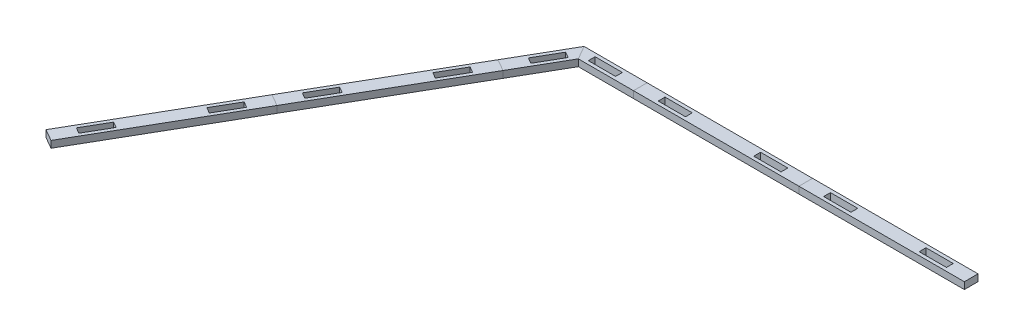
SolidWorks part; units mm, degrees
material "Cedar"
ref_plane "Front Plane" through (0, 0, 0) normal (0, 0, 1) x (1, 0, 0)
ref_plane "Top Plane" through (0, 0, 0) normal (0, 1, 0) x (1, 0, 0)
ref_plane "Right Plane" through (0, 0, 0) normal (1, 0, 0) x (0, 0, -1)
sketch "Sketch1" plane through (0, 0, 0) normal (0, 1, 0) x (1, 0, 0)
  line L0 (-76.9897, 0) -> (76.9897, 0) construction
  line L1 (-76.9897, 0) -> (0, -44.45)
  line L2 (0, -44.45) -> (76.9897, 0)
  line L3 (76.9897, 0) -> (76.9897, 88.9)
  line L4 (76.9897, 88.9) -> (0, 133.35)
  line L5 (0, 133.35) -> (-76.9897, 88.9)
  line L6 (-76.9897, 88.9) -> (-76.9897, 0)
  line L7 (0, -44.45) -> (0, 44.45) construction
  circle A0 centre (0, 44.45) radius 76.9897 construction
  point P9 (0, 0)
  dimension "D1" = 88.9
extrude "Boss-Extrude1" add sketch "Sketch1" against normal blind 6.35
sketch "Sketch2" plane through (0, 0, 0) normal (0, 1, 0) x (1, 0, 0)
  line L0 (-76.9897, 44.45) -> (76.9897, 44.45) construction
  line L1 (-76.9897, 88.9) -> (-76.9897, 0) construction
  line L2 (76.9897, 0) -> (76.9897, 88.9) construction
  point P2 (0, 44.45)
ref_axis "Axis1" through (0, 0, -44.45) along (0, 1, 0)
sketch "Sketch10" plane through (0, 0, 0) normal (0, 1, 0) x (1, 0, 0)
  line L0 (0, -44.45) -> (-21.997, -31.75) construction
  line L1 (-21.997, -31.75) -> (-13.3228, -29.4257)
  line L2 (-13.3228, -29.4257) -> (-35.3198, -16.7257)
  line L3 (-35.3198, -16.7257) -> (-38.4948, -22.225)
  line L4 (-21.997, -31.75) -> (-38.4948, -22.225)
  line L5 (-76.9897, 0) -> (0, -44.45) construction
  dimension "D1" = 45
  dimension "D2" = 6.35
extrude "Cut-Extrude4" cut sketch "Sketch10" against normal through all
sketch "Sketch11" plane through (0, 0, 0) normal (0, 1, 0) x (1, 0, 0)
  line L0 (-38.4948, -22.225) -> (-76.9897, 0) construction
  line L1 (-38.4948, -22.225) -> (-41.6698, -27.7243)
  line L2 (-41.6698, -27.7243) -> (-63.6669, -15.0243)
  line L3 (-63.6669, -15.0243) -> (-54.9926, -12.7)
  line L4 (-54.9926, -12.7) -> (-38.4948, -22.225)
  line L5 (-54.9926, -12.7) -> (-76.9897, 0) construction
  line L6 (-54.9926, -12.7) -> (-76.9897, 0) construction
  line L7 (-76.9897, 0) -> (-38.4948, -22.225) construction
  line L8 (-76.9897, 88.9) -> (-76.9897, 0) construction
  dimension "D1" = 45
  dimension "D2" = 6.35
extrude "Boss-Extrude4" add sketch "Sketch11" against normal blind 6.35
pattern_circular "CirPattern1" count 2 every 60 about axis through (0, 0, -44.45) along (0, 1, 0) of "Cut-Extrude4", "Boss-Extrude4"
sketch "Sketch12" plane through (0, 0, 0) normal (0, 1, 0) x (1, 0, 0)
  line L0 (-76.9897, 12.7) -> (76.9897, 12.7)
  line L1 (-76.9897, 88.9) -> (-76.9897, 0) construction
  line L2 (76.9897, 0) -> (76.9897, 88.9) construction
  line L3 (76.9897, 12.7) -> (76.9897, 133.35)
  line L4 (76.9897, 133.35) -> (-76.9897, 133.35)
  line L5 (-76.9897, 133.35) -> (-76.9897, 12.7)
  line L6 (0, 0) -> (0, 12.7) construction
  dimension "D1" = 12.7
extrude "Cut-Extrude5" cut sketch "Sketch12" against normal through all
sketch "Sketch13" plane through (0, 0, 0) normal (0, 1, 0) x (1, 0, 0)
  line L0 (0, 0) -> (0, 12.7) construction
  line L1 (-76.9897, 12.7) -> (76.9897, 12.7) construction
  line L2 (-44.45, 6.35) -> (44.45, 6.35) construction
  line L4 (-57.15, 9.525) -> (-31.75, 9.525)
  line L5 (-57.15, 9.525) -> (-57.15, 3.175)
  line L6 (-57.15, 3.175) -> (-31.75, 3.175)
  line L7 (-31.75, 9.525) -> (-31.75, 3.175)
  line L8 (-57.15, 9.525) -> (-31.75, 3.175) construction
  line L9 (-57.15, 3.175) -> (-31.75, 9.525) construction
  line L10 (31.75, 9.525) -> (57.15, 9.525)
  line L11 (31.75, 9.525) -> (31.75, 3.175)
  line L12 (31.75, 3.175) -> (57.15, 3.175)
  line L13 (57.15, 9.525) -> (57.15, 3.175)
  line L14 (31.75, 9.525) -> (57.15, 3.175) construction
  line L15 (31.75, 3.175) -> (57.15, 9.525) construction
  point P7 (0, 6.35)
  point P8 (0, 6.35)
  dimension "D1" = 6.35
  dimension "D2" = 25.4
  dimension "D3" = 6.35
  dimension "D4" = 25.4
  dimension "D5" = 88.9
extrude "Cut-Extrude6" cut sketch "Sketch13" against normal through all
pattern_linear "LPattern1" count 5 spacing 153.9793 along (1, 0, 0) count 2 spacing 153.9793 along (-1, 0, 0) pattern seed only yes of bodies 136 131
sketch "Sketch14" plane through (0, 0, 0) normal (0, 1, 0) x (1, 0, 0)
  line L0 (615.9173, -44.45) -> (615.9173, 12.7)
  line L1 (538.9276, 12.7) -> (692.9069, 12.7) construction
  line L2 (615.9173, 12.7) -> (692.9069, 12.7)
  line L3 (692.9069, 12.7) -> (692.9069, -44.45)
  line L4 (692.9069, -44.45) -> (615.9173, -44.45)
  line L5 (-153.9793, -44.45) -> (-153.9793, 12.7)
  line L6 (-230.969, 12.7) -> (-76.9897, 12.7) construction
  line L7 (-153.9793, 12.7) -> (-230.969, 12.7)
  line L8 (-230.969, 12.7) -> (-230.969, -44.45)
  line L9 (-230.969, -44.45) -> (-153.9793, -44.45)
  line L10 (580.5974, -16.7257) -> (597.5864, 12.7)
  line L11 (597.5864, 12.7) -> (615.9173, 12.7)
  line L12 (580.5974, -16.7257) -> (574.2474, -27.7243)
  line L13 (574.2474, -27.7243) -> (615.9173, -44.45)
  line L14 (-112.3095, -27.7243) -> (-135.6484, 12.7)
  line L15 (-135.6484, 12.7) -> (-153.9793, 12.7)
  line L16 (-112.3095, -27.7243) -> (-134.3065, -40.4243)
  line L17 (-134.3065, -40.4243) -> (-153.9793, -44.45)
  line L18 (-118.6595, -16.7257) -> (-112.3095, -27.7243) construction
  line M5 (673.0673, 9.525) -> (673.0673, 3.175)
  line M6 (673.0673, 3.175) -> (647.6673, 3.175)
  line M7 (647.6673, 3.175) -> (647.6673, 9.525)
  line M8 (647.6673, 9.525) -> (673.0673, 9.525)
  line M13 (692.9069, 12.7) -> (538.9276, 12.7)
  line M19 (580.5974, -16.7257) -> (602.5945, -29.4257)
  line M20 (602.5945, -29.4257) -> (593.9202, -31.75)
  line M21 (593.9202, -31.75) -> (615.9173, -44.45)
  line M22 (615.9173, -44.45) -> (637.9143, -31.75)
  line M23 (637.9143, -31.75) -> (635.5901, -40.4243)
  line M24 (635.5901, -40.4243) -> (657.5871, -27.7243)
  line M25 (657.5871, -27.7243) -> (651.2371, -16.7257)
  line M26 (651.2371, -16.7257) -> (673.2341, -4.0257)
  line M27 (673.2341, -4.0257) -> (670.9099, -12.7)
  line M28 (670.9099, -12.7) -> (692.9069, 0)
  line M29 (692.9069, 0) -> (692.9069, 12.7)
extrude "Cut-Extrude7" cut sketch "Sketch14" against normal through all contours L17 L16 L14 L15 L5 | L10 L0 M19 M20 M21 M13 | L0 M22 M23 M24 M25 M26 M27 M28 M29 M13 M8 M5 M6 M7 | L8 L9 L5 L7 region at (603.1355, 0, 12.4572) region at (644.4492, 0, 8.9256) region at (-192.4741, 0, 15.875) region at (-138.3884, 0, 16.3957)
sketch "Sketch15" plane through (0, 0, 0) normal (0, 1, 0) x (1, 0, 0)
  line L0 (-156.381, 0) -> (618.319, 0)
  line L3 (-156.381, 0) -> (-156.381, -63.5)
  line L4 (-156.381, -63.5) -> (618.319, -63.5)
  line L5 (618.319, -63.5) -> (618.319, 0)
  line L6 (230.969, 0) -> (230.969, 12.7)
  line L7 (230.969, 12.7) -> (618.319, 12.7)
  line L8 (618.319, 12.7) -> (618.319, 0)
  point P4 (230.969, 0)
  line M15 (-76.9897, 0) -> (-54.9926, -12.7)
  line M16 (-54.9926, -12.7) -> (-63.6669, -15.0243)
  line M17 (-63.6669, -15.0243) -> (-41.6698, -27.7243)
  line M18 (-41.6698, -27.7243) -> (-35.3198, -16.7257)
  line M19 (-35.3198, -16.7257) -> (-13.3228, -29.4257)
  line M20 (-13.3228, -29.4257) -> (-21.997, -31.75)
  line M21 (-21.997, -31.75) -> (0, -44.45)
  line M22 (0, -44.45) -> (21.997, -31.75)
  line M23 (21.997, -31.75) -> (19.6728, -40.4243)
  line M24 (19.6728, -40.4243) -> (41.6698, -27.7243)
  line M25 (41.6698, -27.7243) -> (35.3198, -16.7257)
  line M26 (35.3198, -16.7257) -> (57.3169, -4.0257)
  line M27 (57.3169, -4.0257) -> (54.9926, -12.7)
  line M28 (54.9926, -12.7) -> (76.9897, 0)
  dimension "D1" = 63.5
  dimension "D2" = 774.7
extrude "Cut-Extrude8" cut sketch "Sketch15" against normal through all contours L8 L7 L6 L0 | L4 L5 L0 L3 M28 M27 M26 M25 M24 M23 M22 M21 M20 M19 M18 M17 M16 M15 | L0 M15 M16 M17 M18 M19 M20 M21 M22 M23 M24 M25 M26 M27 M28 | L5 L0 L3 L4 region at (248.3574, 0, 32.9805) region at (-1.5983, 0, 15.2918) region at (424.644, 0, -6.35)
mirror "Mirror1" about plane through (-96.2371, -6.35, 55.5625) normal (0.866, 0, -0.5) of bodies 151 149 146
